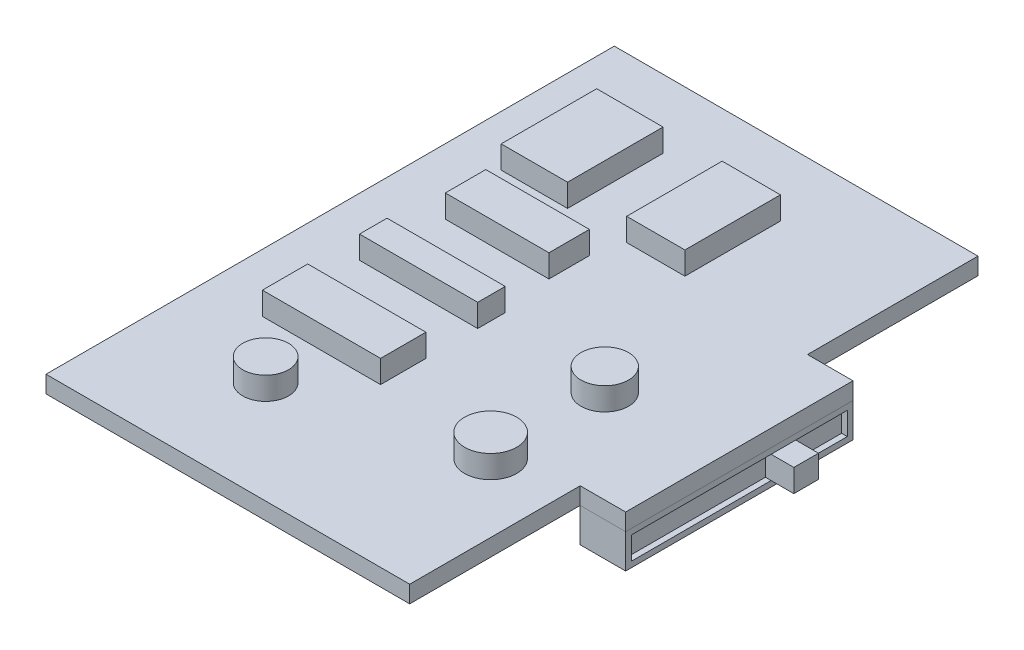
SolidWorks part; units mm, degrees
ref_plane "Front Plane" through (0, 0, 0) normal (0, 0, 1) x (1, 0, 0)
ref_plane "Top Plane" through (0, 0, 0) normal (0, 1, 0) x (1, 0, 0)
ref_plane "Right Plane" through (0, 0, 0) normal (1, 0, 0) x (0, 0, -1)
sketch "Sketch1" plane through (0, 0, 0) normal (0, 1, 0) x (1, 0, 0)
  line L1 (-8, 12.5) -> (8, 12.5)
  line L2 (-8, 12.5) -> (-8, -12.5)
  line L3 (-8, -12.5) -> (8, -12.5)
  line L4 (8, 12.5) -> (8, -12.5)
  line L5 (-8, 12.5) -> (8, -12.5) construction
  line L6 (-8, -12.5) -> (8, 12.5) construction
  line L7 (10, -5) -> (8, -5)
  line L8 (10, -5) -> (10, 5)
  line L9 (10, 5) -> (8, 5)
  line L10 (8, -5) -> (8, 5)
  line L11 (10, -5) -> (8, 5) construction
  line L12 (10, 5) -> (8, -5) construction
  point P0 (0, 0)
  point P6 (9, 0)
  dimension "D1" = 25
  dimension "D2" = 16
  dimension "D3" = 2
  dimension "D4" = 10
extrude "Boss-Extrude1" add sketch "Sketch1" along normal blind 0.75 contours L4 L1 L2 L3 | L8 L9 L4 L7 region at (0, 0, 0) region at (9, 0, 0)
extrude "Boss-Extrude2" add sketch "Sketch1<3>" against normal blind 1.5 separate body contours L8 L9 L4 L7 region at (9, 0, 0)
sketch "Sketch1<3>" plane through (0, 0, 0) normal (0, 1, 0) x (1, 0, 0) same geometry as "Sketch1"
sketch "Sketch3" plane through (10, 0, 0) normal (1, 0, 0) x (0, 0, -1)
  line L11 (4.75, -0.25) -> (-4.75, -0.25)
  line L12 (4.75, -1.25) -> (4.75, -0.25)
  line L13 (-4.75, -1.25) -> (4.75, -1.25)
  line L14 (-4.75, -0.25) -> (-4.75, -1.25)
  line L15 (4.75, -0.25) -> (-4.75, -0.25)
  line L16 (4.75, -1.25) -> (4.75, -0.25)
  line L17 (-4.75, -1.25) -> (4.75, -1.25)
  line L18 (-4.75, -0.25) -> (-4.75, -1.25)
  dimension "D1" = 0.25
extrude "Cut-Extrude1" cut sketch "Sketch3" against normal blind 0.25
sketch "Sketch5" plane through (9.75, 0, 0) normal (1, 0, 0) x (0, 0, -1)
  line L0 (-4.75, -0.75) -> (4.75, -0.75) construction
  line L1 (-4.75, -0.25) -> (-4.75, -1.25) construction
  line L2 (4.75, -1.25) -> (4.75, -0.25) construction
  line L3 (-4.75, -1.25) -> (4.75, -1.25) construction
  line L4 (1.3984, -0.25) -> (2.4822, -0.25)
  line L5 (1.3984, -0.25) -> (1.3984, -1.25)
  line L6 (1.3984, -1.25) -> (2.4822, -1.25)
  line L7 (2.4822, -0.25) -> (2.4822, -1.25)
  line L8 (1.3984, -0.25) -> (2.4822, -1.25) construction
  line L9 (1.3984, -1.25) -> (2.4822, -0.25) construction
  point P7 (1.9403, -0.75)
extrude "Boss-Extrude3" add sketch "Sketch5" along normal blind 1.25
sketch "Sketch6" plane through (0, 0.75, 0) normal (0, 1, 0) x (1, 0, 0)
  line L1 (-2.8443, 5.2879) -> (-5.7642, 5.2879)
  line L2 (-2.8443, 5.2879) -> (-2.8443, 9.4897)
  line L3 (-2.8443, 9.4897) -> (-5.7642, 9.4897)
  line L4 (-5.7642, 5.2879) -> (-5.7642, 9.4897)
  line L5 (-2.8443, 5.2879) -> (-5.7642, 9.4897) construction
  line L6 (-2.8443, 9.4897) -> (-5.7642, 5.2879) construction
  line L7 (2.319, 5.2879) -> (-0.2448, 5.2879)
  line L8 (2.319, 5.2879) -> (2.319, 9.4897)
  line L9 (2.319, 9.4897) -> (-0.2448, 9.4897)
  line L10 (-0.2448, 5.2879) -> (-0.2448, 9.4897)
  line L11 (2.319, 5.2879) -> (-0.2448, 9.4897) construction
  line L12 (2.319, 9.4897) -> (-0.2448, 5.2879) construction
  line L13 (-5.1232, 3.9704) -> (-0.5653, 3.9704)
  line L14 (-5.1232, 3.9704) -> (-5.1232, 2.1899)
  line L15 (-5.1232, 2.1899) -> (-0.5653, 2.1899)
  line L16 (-0.5653, 3.9704) -> (-0.5653, 2.1899)
  line L17 (-5.1232, 3.9704) -> (-0.5653, 2.1899) construction
  line L18 (-5.1232, 2.1899) -> (-0.5653, 3.9704) construction
  line L19 (-5.4437, -0.0534) -> (-0.2448, -0.0534)
  line L20 (-5.4437, -0.0534) -> (-5.4437, -1.2641)
  line L21 (-5.4437, -1.2641) -> (-0.2448, -1.2641)
  line L22 (-0.2448, -0.0534) -> (-0.2448, -1.2641)
  line L23 (-5.4437, -0.0534) -> (-0.2448, -1.2641) construction
  line L24 (-5.4437, -1.2641) -> (-0.2448, -0.0534) construction
  line L25 (-5.4437, -3.5431) -> (-0.2448, -3.5431)
  line L26 (-5.4437, -3.5431) -> (-5.4437, -5.5372)
  line L27 (-5.4437, -5.5372) -> (-0.2448, -5.5372)
  line L28 (-0.2448, -3.5431) -> (-0.2448, -5.5372)
  line L29 (-5.4437, -3.5431) -> (-0.2448, -5.5372) construction
  line L30 (-5.4437, -5.5372) -> (-0.2448, -3.5431) construction
  circle A0 centre (4.9897, -0.908) radius 1.0473
  circle A1 centre (4.9897, -5.9289) radius 1.1467
  circle A2 centre (-2.8443, -7.9942) radius 1.0078
  point P0 (-4.3042, 7.3888)
  point P5 (1.0371, 7.3888)
  point P10 (-2.8443, 3.0802)
  point P15 (-2.8443, -0.6588)
  point P20 (-2.8443, -4.5401)
extrude "Boss-Extrude4" add sketch "Sketch6" along normal blind 1
